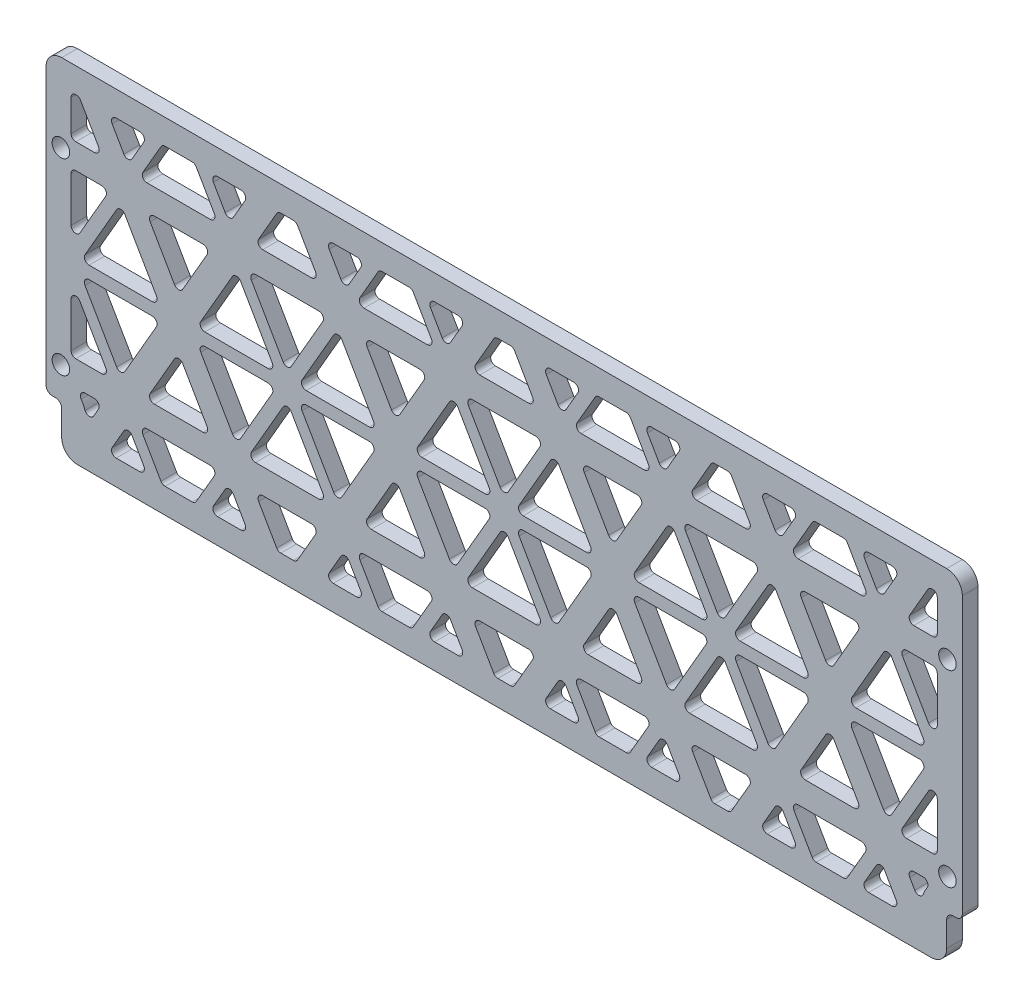
SolidWorks part; units mm, degrees
material "Polyester Resin"
ref_plane "Front Plane" through (0, 0, 0) normal (0, 0, 1) x (1, 0, 0)
ref_plane "Top Plane" through (0, 0, 0) normal (0, 1, 0) x (1, 0, 0)
ref_plane "Right Plane" through (0, 0, 0) normal (1, 0, 0) x (0, 0, -1)
sketch "Sketch1" plane through (0, 0, 0) normal (0, 0, 1) x (1, 0, 0)
  line L2 (-185.7375, 133.35) -> (-185.7375, 21.59)
  line L3 (-173.0375, 0) -> (173.0375, 0)
  line L4 (185.7375, 133.35) -> (185.7375, 21.59)
  line L5 (-179.3875, 139.7) -> (179.3875, 139.7)
  line L8 (0, -55) -> (0, 55) construction
  line L9 (-183.1975, 19.05) -> (-181.9275, 19.05)
  line L10 (-179.3875, 16.51) -> (-179.3875, 6.35)
  line L11 (183.1975, 19.05) -> (181.9275, 19.05)
  line L12 (179.3875, 16.51) -> (179.3875, 6.35)
  line L13 (-179.3875, 139.7) -> (-185.7375, 139.7) construction
  line L14 (-185.7375, 139.7) -> (-185.7375, 133.35) construction
  line L15 (-179.705, 107.95) -> (-179.705, 31.75) construction
  line L16 (179.705, 107.95) -> (179.705, 31.75) construction
  arc A8 (185.7375, 133.35) -> (179.3875, 139.7) centre (179.3875, 133.35) ccw
  arc A9 (-185.7375, 133.35) -> (-179.3875, 139.7) centre (-179.3875, 133.35) cw
  arc A10 (183.1975, 19.05) -> (185.7375, 21.59) centre (183.1975, 21.59) ccw
  arc A11 (181.9275, 19.05) -> (179.3875, 16.51) centre (181.9275, 16.51) ccw
  arc A12 (-181.9275, 19.05) -> (-179.3875, 16.51) centre (-181.9275, 16.51) cw
  arc A13 (-183.1975, 19.05) -> (-185.7375, 21.59) centre (-183.1975, 21.59) cw
  arc A14 (173.0375, 0) -> (179.3875, 6.35) centre (173.0375, 6.35) ccw
  arc A15 (-179.3875, 6.35) -> (-173.0375, 0) centre (-173.0375, 6.35) ccw
  circle A16 centre (-179.705, 31.75) radius 3.556
  circle A17 centre (-179.705, 107.95) radius 3.556
  circle A18 centre (179.705, 107.95) radius 3.556
  circle A19 centre (179.705, 31.75) radius 3.556
  point P22 (185.7375, 19.05)
  point P23 (185.7375, 0)
  point P26 (185.7375, 139.7)
  point P29 (-185.7375, 139.7)
  point P35 (179.3875, 19.05)
  point P38 (-179.3875, 19.05)
  point P41 (-185.7375, 19.05)
  point P44 (179.3875, 0)
  point P47 (-179.3875, 0)
  dimension "D3" = 6.35
  dimension "D4" = 7.112
  dimension "D6" = 6.0325
  dimension "D7" = 6.35
  dimension "D10" = 2.54
  dimension "D11" = 31.75
  dimension "D5" = 76.2
  dimension "D1" = 371.475
  dimension "D2" = 139.7
  dimension "D8" = 19.05
  dimension "D9" = 6.35
extrude "Boss-Extrude1" add sketch "Sketch1" along normal blind 6.35
sketch "Sketch4" plane through (0, 0, 6.35) normal (0, 0, 1) x (1, 0, 0)
  line L0 (-179.705, 31.75) -> (175.5775, 31.75) construction
  line L1 (-175.5775, 69.85) -> (175.5775, 69.85) construction
  line L2 (0, -3.4925) -> (0, 3.4925) construction
  line L3 (-43.9941, 69.85) -> (-65.9911, 107.95) construction
  line L4 (-65.9911, 107.95) -> (-109.9852, 107.95) construction
  line L5 (-109.9852, 107.95) -> (-131.9823, 69.85) construction
  line L6 (-131.9823, 69.85) -> (-109.9852, 31.75) construction
  line L7 (-109.9852, 31.75) -> (-65.9911, 31.75) construction
  line L8 (-179.705, 107.95) -> (175.5775, 107.95) construction
  line L9 (-65.9911, 31.75) -> (-43.9941, 69.85) construction
  line L10 (-43.9941, 69.85) -> (-21.997, 31.75) construction
  line L11 (-21.997, 31.75) -> (21.997, 31.75) construction
  line L12 (21.997, 31.75) -> (43.9941, 69.85) construction
  line L13 (43.9941, 69.85) -> (21.997, 107.95) construction
  line L14 (21.997, 107.95) -> (-21.997, 107.95) construction
  line L15 (-21.997, 107.95) -> (-43.9941, 69.85) construction
  line L16 (-175.5775, 129.54) -> (-175.5775, 27.5085)
  line L17 (-169.2275, 16.51) -> (-169.2275, 10.16)
  line L18 (-169.2275, 10.16) -> (169.2275, 10.16)
  line L19 (169.2275, 10.16) -> (169.2275, 16.51)
  line L20 (175.5775, 27.5085) -> (175.5775, 129.54)
  line L21 (175.5775, 129.54) -> (-175.5775, 129.54)
  line L22 (-175.5775, 129.54) -> (-175.5775, 27.5085)
  line L23 (-169.2275, 16.51) -> (-169.2275, 10.16)
  line L24 (-169.2275, 10.16) -> (169.2275, 10.16)
  line L25 (169.2275, 10.16) -> (169.2275, 16.51)
  line L26 (175.5775, 27.5085) -> (175.5775, 129.54)
  line L27 (175.5775, 129.54) -> (-175.5775, 129.54)
  line L28 (43.9941, 69.85) -> (65.9911, 31.75) construction
  line L29 (65.9911, 31.75) -> (109.9852, 31.75) construction
  line L30 (109.9852, 31.75) -> (131.9823, 69.85) construction
  line L31 (131.9823, 69.85) -> (109.9852, 107.95) construction
  line L32 (109.9852, 107.95) -> (65.9911, 107.95) construction
  line L33 (65.9911, 107.95) -> (43.9941, 69.85) construction
  line L34 (131.9823, 69.85) -> (153.9793, 31.75) construction
  line L35 (153.9793, 31.75) -> (197.9734, 31.75) construction
  line L36 (197.9734, 31.75) -> (219.9705, 69.85) construction
  line L37 (219.9705, 69.85) -> (197.9734, 107.95) construction
  line L38 (197.9734, 107.95) -> (153.9793, 107.95) construction
  line L39 (153.9793, 107.95) -> (131.9823, 69.85) construction
  line L40 (-131.9823, 69.85) -> (-153.9793, 107.95) construction
  line L41 (-153.9793, 107.95) -> (-197.9734, 107.95) construction
  line L42 (-197.9734, 107.95) -> (-219.9705, 69.85) construction
  line L43 (-219.9705, 69.85) -> (-197.9734, 31.75) construction
  line L44 (-197.9734, 31.75) -> (-153.9793, 31.75) construction
  line L45 (-153.9793, 31.75) -> (-131.9823, 69.85) construction
  line L46 (-43.9941, -6.35) -> (-65.9911, 31.75) construction
  line L47 (-65.9911, 31.75) -> (-109.9852, 31.75) construction
  line L48 (-109.9852, 31.75) -> (-131.9823, -6.35) construction
  line L49 (-131.9823, -6.35) -> (-109.9852, -44.45) construction
  line L50 (-109.9852, -44.45) -> (-65.9911, -44.45) construction
  line L51 (-65.9911, -44.45) -> (-43.9941, -6.35) construction
  line L52 (-131.9823, -6.35) -> (-153.9793, 31.75) construction
  line L53 (-153.9793, 31.75) -> (-197.9734, 31.75) construction
  line L54 (-197.9734, 31.75) -> (-219.9705, -6.35) construction
  line L55 (-219.9705, -6.35) -> (-197.9734, -44.45) construction
  line L56 (-197.9734, -44.45) -> (-153.9793, -44.45) construction
  line L57 (-153.9793, -44.45) -> (-131.9823, -6.35) construction
  line L58 (-43.9941, -6.35) -> (-21.997, -44.45) construction
  line L59 (-21.997, -44.45) -> (21.997, -44.45) construction
  line L60 (21.997, -44.45) -> (43.9941, -6.35) construction
  line L61 (43.9941, -6.35) -> (21.997, 31.75) construction
  line L62 (21.997, 31.75) -> (-21.997, 31.75) construction
  line L63 (-21.997, 31.75) -> (-43.9941, -6.35) construction
  line L64 (43.9941, -6.35) -> (65.9911, -44.45) construction
  line L65 (65.9911, -44.45) -> (109.9852, -44.45) construction
  line L66 (109.9852, -44.45) -> (131.9823, -6.35) construction
  line L67 (131.9823, -6.35) -> (109.9852, 31.75) construction
  line L68 (109.9852, 31.75) -> (65.9911, 31.75) construction
  line L69 (65.9911, 31.75) -> (43.9941, -6.35) construction
  line L70 (131.9823, -6.35) -> (153.9793, -44.45) construction
  line L71 (153.9793, -44.45) -> (197.9734, -44.45) construction
  line L72 (197.9734, -44.45) -> (219.9705, -6.35) construction
  line L73 (219.9705, -6.35) -> (197.9734, 31.75) construction
  line L74 (197.9734, 31.75) -> (153.9793, 31.75) construction
  line L75 (153.9793, 31.75) -> (131.9823, -6.35) construction
  line L76 (-43.9941, 69.85) -> (-65.9911, 107.95) construction
  line L77 (-65.9911, 107.95) -> (-109.9852, 107.95) construction
  line L78 (-109.9852, 107.95) -> (-131.9823, 69.85) construction
  line L79 (-131.9823, 69.85) -> (-109.9852, 31.75) construction
  line L80 (-109.9852, 31.75) -> (-65.9911, 31.75) construction
  line L81 (-65.9911, 31.75) -> (-43.9941, 69.85) construction
  line L82 (-131.9823, 69.85) -> (-153.9793, 107.95) construction
  line L83 (-153.9793, 107.95) -> (-197.9734, 107.95) construction
  line L84 (-197.9734, 107.95) -> (-219.9705, 69.85) construction
  line L85 (-219.9705, 69.85) -> (-197.9734, 31.75) construction
  line L86 (-197.9734, 31.75) -> (-153.9793, 31.75) construction
  line L87 (-153.9793, 31.75) -> (-131.9823, 69.85) construction
  line L88 (-43.9941, 69.85) -> (-21.997, 31.75) construction
  line L89 (-21.997, 31.75) -> (21.997, 31.75) construction
  line L90 (21.997, 31.75) -> (43.9941, 69.85) construction
  line L91 (43.9941, 69.85) -> (21.997, 107.95) construction
  line L92 (21.997, 107.95) -> (-21.997, 107.95) construction
  line L93 (-21.997, 107.95) -> (-43.9941, 69.85) construction
  line L94 (43.9941, 69.85) -> (65.9911, 31.75) construction
  line L95 (65.9911, 31.75) -> (109.9852, 31.75) construction
  line L96 (109.9852, 31.75) -> (131.9823, 69.85) construction
  line L97 (131.9823, 69.85) -> (109.9852, 107.95) construction
  line L98 (109.9852, 107.95) -> (65.9911, 107.95) construction
  line L99 (65.9911, 107.95) -> (43.9941, 69.85) construction
  line L100 (131.9823, 69.85) -> (153.9793, 31.75) construction
  line L101 (153.9793, 31.75) -> (197.9734, 31.75) construction
  line L102 (197.9734, 31.75) -> (219.9705, 69.85) construction
  line L103 (219.9705, 69.85) -> (197.9734, 107.95) construction
  line L104 (197.9734, 107.95) -> (153.9793, 107.95) construction
  line L105 (153.9793, 107.95) -> (131.9823, 69.85) construction
  line L106 (-43.9941, 146.05) -> (-65.9911, 184.15) construction
  line L107 (-65.9911, 184.15) -> (-109.9852, 184.15) construction
  line L108 (-109.9852, 184.15) -> (-131.9823, 146.05) construction
  line L109 (-131.9823, 146.05) -> (-109.9852, 107.95) construction
  line L110 (-109.9852, 107.95) -> (-65.9911, 107.95) construction
  line L111 (-65.9911, 107.95) -> (-43.9941, 146.05) construction
  line L112 (-131.9823, 146.05) -> (-153.9793, 184.15) construction
  line L113 (-153.9793, 184.15) -> (-197.9734, 184.15) construction
  line L114 (-197.9734, 184.15) -> (-219.9705, 146.05) construction
  line L115 (-219.9705, 146.05) -> (-197.9734, 107.95) construction
  line L116 (-197.9734, 107.95) -> (-153.9793, 107.95) construction
  line L117 (-153.9793, 107.95) -> (-131.9823, 146.05) construction
  line L118 (-43.9941, 146.05) -> (-21.997, 107.95) construction
  line L119 (-21.997, 107.95) -> (21.997, 107.95) construction
  line L120 (21.997, 107.95) -> (43.9941, 146.05) construction
  line L121 (43.9941, 146.05) -> (21.997, 184.15) construction
  line L122 (21.997, 184.15) -> (-21.997, 184.15) construction
  line L123 (-21.997, 184.15) -> (-43.9941, 146.05) construction
  line L124 (43.9941, 146.05) -> (65.9911, 107.95) construction
  line L125 (65.9911, 107.95) -> (109.9852, 107.95) construction
  line L126 (109.9852, 107.95) -> (131.9823, 146.05) construction
  line L127 (131.9823, 146.05) -> (109.9852, 184.15) construction
  line L128 (109.9852, 184.15) -> (65.9911, 184.15) construction
  line L129 (65.9911, 184.15) -> (43.9941, 146.05) construction
  line L130 (131.9823, 146.05) -> (153.9793, 107.95) construction
  line L131 (153.9793, 107.95) -> (197.9734, 107.95) construction
  line L132 (197.9734, 107.95) -> (219.9705, 146.05) construction
  line L133 (219.9705, 146.05) -> (197.9734, 184.15) construction
  line L134 (197.9734, 184.15) -> (153.9793, 184.15) construction
  line L135 (153.9793, 184.15) -> (131.9823, 146.05) construction
  line L136 (-197.9734, 184.15) -> (-65.9911, -44.45) construction
  line L137 (-109.9852, 184.15) -> (21.997, -44.45) construction
  line L138 (-21.997, 184.15) -> (109.9852, -44.45) construction
  line L139 (65.9911, 184.15) -> (197.9734, -44.45) construction
  line L140 (153.9793, 184.15) -> (197.9734, 107.95) construction
  line L141 (-197.9734, 31.75) -> (-153.9793, -44.45) construction
  line L142 (-197.9734, 107.95) -> (-153.9793, 184.15) construction
  line L143 (-197.9734, 107.95) -> (-153.9793, 31.75) construction
  line L144 (-109.9852, 107.95) -> (-65.9911, 31.75) construction
  line L145 (-21.997, 107.95) -> (21.997, 31.75) construction
  line L146 (65.9911, 107.95) -> (109.9852, 31.75) construction
  line L147 (153.9793, 107.95) -> (197.9734, 31.75) construction
  line L148 (-197.9734, 31.75) -> (-153.9793, 107.95) construction
  line L149 (-21.997, 31.75) -> (21.997, 107.95) construction
  line L150 (-197.9734, -44.45) -> (-65.9911, 184.15) construction
  line L151 (-109.9852, 31.75) -> (-65.9911, 107.95) construction
  line L152 (-109.9852, -44.45) -> (21.997, 184.15) construction
  line L153 (-21.997, -44.45) -> (109.9852, 184.15) construction
  line L154 (65.9911, -44.45) -> (197.9734, 184.15) construction
  line L155 (65.9911, 31.75) -> (109.9852, 107.95) construction
  line L156 (153.9793, 31.75) -> (197.9734, 107.95) construction
  line L157 (153.9793, -44.45) -> (197.9734, 31.75) construction
  line L158 (-179.705, 102.87) -> (175.5775, 102.87)
  line L159 (-179.705, 26.67) -> (175.5775, 26.67)
  line L160 (-127.5829, 72.39) -> (-149.5799, 110.49)
  line L161 (-149.5799, 29.21) -> (-127.5829, 67.31)
  line L162 (-136.3817, 67.31) -> (-114.3846, 29.21)
  line L163 (-114.3846, 110.49) -> (-136.3817, 72.39)
  line L164 (-193.574, -46.99) -> (-61.5917, 181.61)
  line L165 (-202.3728, 181.61) -> (-70.3905, -46.99)
  line L166 (-105.5858, -46.99) -> (26.3965, 181.61)
  line L167 (-114.3846, 181.61) -> (17.5976, -46.99)
  line L168 (-17.5976, -46.99) -> (114.3846, 181.61)
  line L169 (61.5917, 181.61) -> (193.574, -46.99)
  line L170 (70.3905, -46.99) -> (202.3728, 181.61)
  line L171 (-26.3965, 181.61) -> (105.5858, -46.99)
  line L172 (-179.705, 113.03) -> (175.5775, 113.03)
  line L173 (-179.705, 36.83) -> (175.5775, 36.83)
  line L174 (-136.3817, 67.31) -> (-158.3787, 105.41)
  line L175 (-158.3787, 34.29) -> (-136.3817, 72.39)
  line L176 (-127.5829, 72.39) -> (-105.5858, 34.29)
  line L177 (-105.5858, 105.41) -> (-127.5829, 67.31)
  line L178 (-202.3728, -41.91) -> (-70.3905, 186.69)
  line L179 (-193.574, 186.69) -> (-61.5917, -41.91)
  line L180 (-114.3846, -41.91) -> (17.5976, 186.69)
  line L181 (-105.5858, 186.69) -> (26.3965, -41.91)
  line L182 (-26.3965, -41.91) -> (105.5858, 186.69)
  line L183 (70.3905, 186.69) -> (202.3728, -41.91)
  line L184 (61.5917, -41.91) -> (193.574, 186.69)
  line L185 (-17.5976, 186.69) -> (114.3846, -41.91)
  line L186 (-151.7796, 106.68) -> (-131.9823, 140.97)
  line L187 (-131.9823, 140.97) -> (-112.1849, 106.68)
  line L188 (-112.1849, 106.68) -> (-68.1908, 30.48)
  line L189 (-195.7737, 30.48) -> (-151.7796, 106.68)
  line L190 (-175.5775, 67.31) -> (175.5775, 67.31)
  line L191 (-200.1731, 106.68) -> (-156.179, 30.48)
  line L192 (-112.1849, 33.02) -> (-131.9823, -1.27)
  line L193 (-131.9823, -1.27) -> (-151.7796, 33.02)
  line L194 (-107.7855, 30.48) -> (-63.7914, 106.68)
  line L195 (-63.7914, 106.68) -> (-43.9941, 140.97)
  line L196 (-43.9941, 140.97) -> (-24.1967, 106.68)
  line L197 (-24.1967, 33.02) -> (-43.9941, -1.27)
  line L198 (-43.9941, -1.27) -> (-63.7914, 33.02)
  line L199 (-19.7973, 30.48) -> (24.1967, 106.68)
  line L200 (24.1967, 106.68) -> (43.9941, 140.97)
  line L201 (43.9941, 140.97) -> (63.7914, 106.68)
  line L202 (-24.1967, 106.68) -> (19.7973, 30.48)
  line L203 (63.7914, 33.02) -> (43.9941, -1.27)
  line L204 (43.9941, -1.27) -> (24.1967, 33.02)
  line L205 (68.1908, 30.48) -> (112.1849, 106.68)
  line L206 (112.1849, 106.68) -> (131.9823, 140.97)
  line L207 (131.9823, 140.97) -> (151.7796, 106.68)
  line L208 (151.7796, 106.68) -> (195.7737, 30.48)
  line L209 (63.7914, 106.68) -> (107.7855, 30.48)
  line L210 (131.9823, -11.43) -> (107.7855, 30.48)
  line L211 (156.179, 30.48) -> (131.9823, -11.43)
  line L212 (156.179, 30.48) -> (200.1731, 106.68)
  line L213 (-156.179, 109.22) -> (-131.9823, 151.13)
  line L214 (-131.9823, 151.13) -> (-107.7855, 109.22)
  line L215 (-107.7855, 109.22) -> (-63.7914, 33.02)
  line L216 (-200.1731, 33.02) -> (-156.179, 109.22)
  line L217 (-175.5775, 72.39) -> (175.5775, 72.39)
  line L218 (-195.7737, 109.22) -> (-151.7796, 33.02)
  line L219 (-107.7855, 30.48) -> (-131.9823, -11.43)
  line L220 (-131.9823, -11.43) -> (-156.179, 30.48)
  line L221 (-112.1849, 33.02) -> (-68.1908, 109.22)
  line L222 (-68.1908, 109.22) -> (-43.9941, 151.13)
  line L223 (-43.9941, 151.13) -> (-19.7973, 109.22)
  line L224 (-19.7973, 30.48) -> (-43.9941, -11.43)
  line L225 (-43.9941, -11.43) -> (-68.1908, 30.48)
  line L226 (-24.1967, 33.02) -> (19.7973, 109.22)
  line L227 (19.7973, 109.22) -> (43.9941, 151.13)
  line L228 (43.9941, 151.13) -> (68.1908, 109.22)
  line L229 (-19.7973, 109.22) -> (24.1967, 33.02)
  line L230 (68.1908, 30.48) -> (43.9941, -11.43)
  line L231 (43.9941, -11.43) -> (19.7973, 30.48)
  line L232 (63.7914, 33.02) -> (107.7855, 109.22)
  line L233 (107.7855, 109.22) -> (131.9823, 151.13)
  line L234 (131.9823, 151.13) -> (156.179, 109.22)
  line L235 (156.179, 109.22) -> (200.1731, 33.02)
  line L236 (68.1908, 109.22) -> (112.1849, 33.02)
  line L237 (131.9823, -1.27) -> (112.1849, 33.02)
  line L238 (151.7796, 33.02) -> (131.9823, -1.27)
  line L239 (151.7796, 33.02) -> (195.7737, 109.22)
  circle A0 centre (-179.705, 107.95) radius 3.556 construction
  circle A1 centre (-87.9882, 69.85) radius 38.1 construction
  circle A2 centre (0, 69.85) radius 38.1 construction
  circle A3 centre (87.9882, 69.85) radius 38.1 construction
  circle A4 centre (175.9764, 69.85) radius 38.1 construction
  circle A5 centre (-175.9764, 69.85) radius 38.1 construction
  arc A16 (-169.2275, 16.51) -> (-175.5775, 27.5085) centre (-181.9275, 16.51) ccw
  arc A17 (175.5775, 27.5085) -> (169.2275, 16.51) centre (181.9275, 16.51) ccw
  arc A18 (-169.2275, 16.51) -> (-175.5775, 27.5085) centre (-181.9275, 16.51) ccw
  arc A19 (175.5775, 27.5085) -> (169.2275, 16.51) centre (181.9275, 16.51) ccw
  point P37 (0, 0)
  dimension "D2" = 38.1
  dimension "D5" = 38.1
  dimension "D6" = 5.08
  dimension "D1" = 10.16
  dimension "D7" = 5.08
  dimension "D8" = 2.54
  dimension "D9" = 2.54
  dimension "D3" = 2
  dimension "D4" = 2
extrude "Cut-Extrude2" cut sketch "Sketch4" against normal through all contours L22 L172 L165 L27 | L22 L216 L158 | A18 L23 L178 L159 | L190 L218 L178 | L24 L220 L164 | L193 L24 L192 L159 | L164 L173 L162 | L179 L221 L190 | L177 L217 L188 | L163 L158 L160 | L187 L27 L186 L172 | L27 L214 L178 | L215 L221 L158 | L194 L217 L167 | L190 L215 L180 | L194 L173 L188 | L24 L180 L159 L179 | L165 L219 L24 | L198 L24 L197 L159 | L24 L225 L166 | L166 L173 L167 | L24 L182 L159 L181 | L167 L224 L24 | L202 L199 L173 | L181 L226 L190 | L158 L229 L226 | L166 L217 L202 | L158 L181 L180 | L196 L27 L195 L172 | L181 L222 L27 | L185 L227 L27 | L201 L27 L200 L172 | L158 L185 L182 | L199 L217 L171 | L190 L229 L182 | L168 L173 L171 | L204 L24 L203 L159 | L24 L231 L168 | L171 L230 L24 | L209 L205 L173 | L185 L232 L190 | L168 L217 L209 | L189 L217 L174 | L164 L172 L167 L27 | L166 L172 L171 L27 | L190 L236 L184 | L205 L217 L169 | L158 L236 L232 | L207 L27 L206 L172 | L183 L184 L158 | L170 L217 L208 | L158 L235 L26 | L183 L239 L190 | L170 L173 L169 | L238 L159 L237 L24 | L169 L211 L24 | L212 L173 L26 | L168 L172 L169 L27 | L159 L185 L24 L184 | L24 L210 L170 | L170 L172 L26 L27 | L27 L234 L184 | L183 L233 L27 | L27 L228 L182 | L27 L223 L180 | L179 L213 L27 | L191 L22 L173 | A19 L159 L183 L25 region at (-170.3334, 93.7869, 6.35) region at (-155.4458, 81.7033, 6.35) region at (-170.3334, 45.9131, 6.35) region at (-155.4458, 57.9967, 6.35) region at (-171.0896, 119.6525, 6.35) region at (-131.9823, 95.25, 6.35) region at (-168.1634, 23.3371, 6.35) region at (-131.9823, 44.45, 6.35) region at (-108.5188, 81.7033, 6.35) region at (-108.5188, 57.9967, 6.35) region at (-152.5128, 124.8833, 6.35) region at (-131.9823, 120.1311, 6.35) region at (-152.5128, 14.8167, 6.35) region at (-131.9823, 19.5689, 6.35) region at (-87.9882, 93.5567, 6.35) region at (-111.4517, 124.8833, 6.35) region at (-111.4517, 14.8167, 6.35) region at (-87.9882, 46.1433, 6.35) region at (-87.9882, 119.7297, 6.35) region at (-67.4576, 81.7033, 6.35) region at (-87.9882, 19.9703, 6.35) region at (-67.4576, 57.9967, 6.35) region at (-43.9941, 95.25, 6.35) region at (-64.5247, 124.8833, 6.35) region at (-64.5247, 14.8167, 6.35) region at (-43.9941, 44.45, 6.35) region at (-43.9941, 120.1311, 6.35) region at (-20.5306, 81.7033, 6.35) region at (-43.9941, 19.5689, 6.35) region at (-20.5306, 57.9967, 6.35) region at (-23.4635, 124.8833, 6.35) region at (-23.4635, 14.8167, 6.35) region at (0, 93.5567, 6.35) region at (0, 46.1433, 6.35) region at (0, 119.7297, 6.35) region at (20.5306, 81.7033, 6.35) region at (0, 19.9703, 6.35) region at (20.5306, 57.9967, 6.35) region at (23.4635, 124.8833, 6.35) region at (23.4635, 14.8167, 6.35) region at (43.9941, 95.25, 6.35) region at (43.9941, 44.45, 6.35) region at (43.9941, 120.1311, 6.35) region at (67.4576, 81.7033, 6.35) region at (43.9941, 19.5689, 6.35) region at (67.4576, 57.9967, 6.35) region at (64.5247, 124.8833, 6.35) region at (64.5247, 14.8167, 6.35) region at (87.9882, 93.5567, 6.35) region at (87.9882, 119.7297, 6.35) region at (87.9882, 19.9703, 6.35) region at (87.9882, 46.1433, 6.35) region at (108.5188, 81.7033, 6.35) region at (108.5188, 57.9967, 6.35) region at (111.4517, 124.8833, 6.35) region at (111.4517, 14.8167, 6.35) region at (131.9823, 95.25, 6.35) region at (131.9823, 120.1311, 6.35) region at (131.9823, 19.5689, 6.35) region at (131.9823, 44.45, 6.35)
fillet "Fillet1" radius 1.905 220 edges at (169.2275, 15.4994, 3.175) (-169.2275, 15.4994, 3.175) (175.5775, 64.0792, 3.175) (-175.5775, 64.0792, 3.175) (-152.5128, 24.13, 3.175) (-111.4517, 24.13, 3.175) (-64.5247, 24.13, 3.175) (-23.4635, 24.13, 3.175) (152.5128, 24.13, 3.175) (111.4517, 24.13, 3.175) (64.5247, 24.13, 3.175) (23.4635, 24.13, 3.175) (144.4473, 10.16, 3.175) (125.3832, 10.16, 3.175) (103.3861, 10.16, 3.175) (56.4591, 10.16, 3.175) (84.322, 10.16, 3.175) (37.395, 10.16, 3.175) (15.3979, 10.16, 3.175) (-3.6662, 10.16, 3.175) (-31.5291, 10.16, 3.175) (-50.5932, 10.16, 3.175) (-72.5902, 10.16, 3.175) (-91.6544, 10.16, 3.175) (-119.5173, 10.16, 3.175) (-138.5814, 10.16, 3.175) (-160.5784, 10.16, 3.175) (139.3146, 72.39, 3.175) (92.3876, 72.39, 3.175) (51.3264, 72.39, 3.175) (4.3994, 72.39, 3.175) (-36.6617, 72.39, 3.175) (-83.5888, 72.39, 3.175) (-124.6499, 72.39, 3.175) (-171.577, 72.39, 3.175) (159.8452, 36.83, 3.175) (118.784, 36.83, 3.175) (71.857, 36.83, 3.175) (30.7959, 36.83, 3.175) (-16.1312, 36.83, 3.175) (-57.1923, 36.83, 3.175) (-104.1193, 36.83, 3.175) (-145.1805, 36.83, 3.175) (-144.4473, 10.16, 3.175) (-125.3832, 10.16, 3.175) (-103.3861, 10.16, 3.175) (-84.322, 10.16, 3.175) (-56.4591, 10.16, 3.175) (-37.395, 10.16, 3.175) (-15.3979, 10.16, 3.175) (3.6662, 10.16, 3.175) (31.5291, 10.16, 3.175) (50.5932, 10.16, 3.175) (72.5902, 10.16, 3.175) (91.6544, 10.16, 3.175) (119.5173, 10.16, 3.175) (138.5814, 10.16, 3.175) (160.5784, 10.16, 3.175) (-159.8452, 36.83, 3.175) (-118.784, 36.83, 3.175) (-71.857, 36.83, 3.175) (-30.7959, 36.83, 3.175) (16.1312, 36.83, 3.175) (57.1923, 36.83, 3.175) (104.1193, 36.83, 3.175) (145.1805, 36.83, 3.175) (-4.3994, 72.39, 3.175) (36.6617, 72.39, 3.175) (83.5888, 72.39, 3.175) (124.6499, 72.39, 3.175) (171.577, 72.39, 3.175) (-51.3264, 72.39, 3.175) (-92.3876, 72.39, 3.175) (-139.3146, 72.39, 3.175) (-155.4458, 100.33, 3.175) (-131.9823, 59.69, 3.175) (-108.5188, 100.33, 3.175) (-87.9882, 64.77, 3.175) (-67.4576, 100.33, 3.175) (-43.9941, 59.69, 3.175) (-20.5306, 100.33, 3.175) (20.5306, 100.33, 3.175) (67.4576, 100.33, 3.175) (0, 64.77, 3.175) (43.9941, 59.69, 3.175) (87.9882, 64.77, 3.175) (131.9823, 59.69, 3.175) (108.5188, 100.33, 3.175) (155.4458, 100.33, 3.175) (175.5775, 36.83, 3.175) (-175.5775, 36.83, 3.175) (-175.5775, 75.6208, 3.175) (-131.9823, 80.01, 3.175) (-87.9882, 74.93, 3.175) (-43.9941, 80.01, 3.175) (0, 74.93, 3.175) (175.5775, 75.6208, 3.175) (131.9823, 80.01, 3.175) (87.9882, 74.93, 3.175) (43.9941, 80.01, 3.175) (155.4458, 39.37, 3.175) (108.5188, 39.37, 3.175) (67.4576, 39.37, 3.175) (20.5306, 39.37, 3.175) (-20.5306, 39.37, 3.175) (-67.4576, 39.37, 3.175) (-108.5188, 39.37, 3.175) (-155.4458, 39.37, 3.175) (-162.7781, 26.67, 3.175) (162.7781, 26.67, 3.175) (174.3075, 26.67, 3.175) (148.1134, 26.67, 3.175) (101.1864, 26.67, 3.175) (60.1253, 26.67, 3.175) (13.1982, 26.67, 3.175) (-27.8629, 26.67, 3.175) (-74.79, 26.67, 3.175) (-115.8511, 26.67, 3.175) (-139.3146, 67.31, 3.175) (-92.3876, 67.31, 3.175) (-51.3264, 67.31, 3.175) (-4.3994, 67.31, 3.175) (36.6617, 67.31, 3.175) (83.5888, 67.31, 3.175) (124.6499, 67.31, 3.175) (171.577, 67.31, 3.175) (175.5775, 102.87, 3.175) (145.1805, 102.87, 3.175) (104.1193, 102.87, 3.175) (57.1923, 102.87, 3.175) (16.1312, 102.87, 3.175) (-30.7959, 102.87, 3.175) (-71.857, 102.87, 3.175) (-118.784, 102.87, 3.175) (-159.8452, 102.87, 3.175) (-174.3075, 26.67, 3.175) (-148.1134, 26.67, 3.175) (-101.1864, 26.67, 3.175) (-60.1253, 26.67, 3.175) (-13.1982, 26.67, 3.175) (27.8629, 26.67, 3.175) (74.79, 26.67, 3.175) (115.8511, 26.67, 3.175) (139.3146, 67.31, 3.175) (92.3876, 67.31, 3.175) (51.3264, 67.31, 3.175) (4.3994, 67.31, 3.175) (-36.6617, 67.31, 3.175) (-83.5888, 67.31, 3.175) (-124.6499, 67.31, 3.175) (-171.577, 67.31, 3.175) (159.8452, 102.87, 3.175) (118.784, 102.87, 3.175) (71.857, 102.87, 3.175) (30.7959, 102.87, 3.175) (-16.1312, 102.87, 3.175) (-57.1923, 102.87, 3.175) (-104.1193, 102.87, 3.175) (-145.1805, 102.87, 3.175) (-175.5775, 102.87, 3.175) (162.7781, 113.03, 3.175) (175.5775, 113.03, 3.175) (175.5775, 129.54, 3.175) (172.3102, 129.54, 3.175) (144.4473, 129.54, 3.175) (160.5784, 129.54, 3.175) (152.5128, 115.57, 3.175) (115.8511, 113.03, 3.175) (148.1134, 113.03, 3.175) (138.5814, 129.54, 3.175) (125.3832, 129.54, 3.175) (103.3861, 129.54, 3.175) (119.5173, 129.54, 3.175) (111.4517, 115.57, 3.175) (74.79, 113.03, 3.175) (101.1864, 113.03, 3.175) (91.6544, 129.54, 3.175) (84.322, 129.54, 3.175) (56.4591, 129.54, 3.175) (72.5902, 129.54, 3.175) (64.5247, 115.57, 3.175) (27.8629, 113.03, 3.175) (60.1253, 113.03, 3.175) (50.5932, 129.54, 3.175) (37.395, 129.54, 3.175) (15.3979, 129.54, 3.175) (31.5291, 129.54, 3.175) (23.4635, 115.57, 3.175) (-13.1982, 113.03, 3.175) (13.1982, 113.03, 3.175) (-3.6662, 129.54, 3.175) (3.6662, 129.54, 3.175) (-31.5291, 129.54, 3.175) (-15.3979, 129.54, 3.175) (-23.4635, 115.57, 3.175) (-60.1253, 113.03, 3.175) (-27.8629, 113.03, 3.175) (-50.5932, 129.54, 3.175) (-37.395, 129.54, 3.175) (-64.5247, 115.57, 3.175) (-72.5902, 129.54, 3.175) (-56.4591, 129.54, 3.175) (-101.1864, 113.03, 3.175) (-91.6544, 129.54, 3.175) (-84.322, 129.54, 3.175) (-74.79, 113.03, 3.175) (-111.4517, 115.57, 3.175) (-119.5173, 129.54, 3.175) (-103.3861, 129.54, 3.175) (-115.8511, 113.03, 3.175) (-148.1134, 113.03, 3.175) (-138.5814, 129.54, 3.175) (-125.3832, 129.54, 3.175) (-152.5128, 115.57, 3.175) (-160.5784, 129.54, 3.175) (-144.4473, 129.54, 3.175) (-162.7781, 113.03, 3.175) (-175.5775, 113.03, 3.175) (-172.3102, 129.54, 3.175) (-175.5775, 129.54, 3.175)
